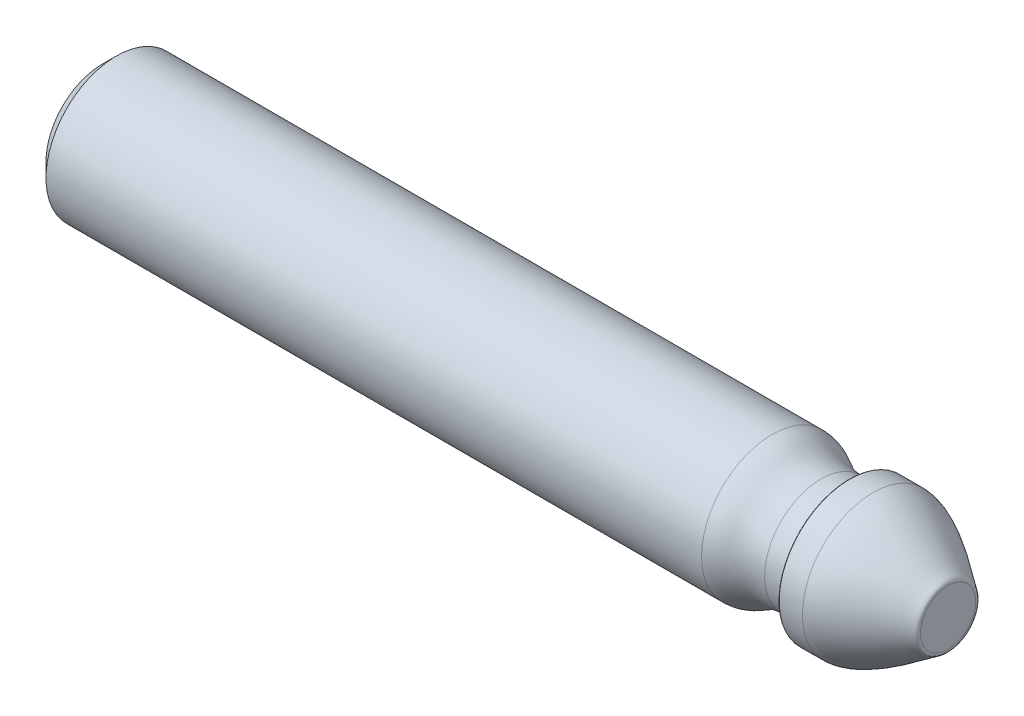
SolidWorks part; units mm, degrees
material "Alloy Steel"
ref_plane "Front" through (0, 0, 0) normal (0, 0, 1) x (1, 0, 0)
ref_plane "Top" through (0, 0, 0) normal (0, 1, 0) x (1, 0, 0)
ref_plane "Right" through (0, 0, 0) normal (1, 0, 0) x (0, 0, -1)
sketch "Sketch1" plane through (0, 0, 0) normal (0, 0, 1) x (1, 0, 0)
  line L0 (-19.05, 0) -> (19.05, 0) construction
  line L1 (19.05, 3.175) -> (19.05, -3.175) construction
  line L2 (-19.05, 3.175) -> (-19.05, -3.175) construction
  dimension "Length" = 38.1
  dimension "Diameter" = 6.35
sketch "Sketch2" plane through (0, 0, 0) normal (1, 0, 0) x (0, 0, -1)
  circle A0 centre (0, 0) radius 3.175
extrude "Extrude1" add sketch "Sketch2" against normal up to vertex (19.05 mm away) and the other way up to vertex (19.05 mm away) up to point (-19.05, 3.175, 0) other way up to point (19.05, 3.175, 0)
chamfer "Chamfer1" distance 0.635 angle 45 2 edges at (19.05, 0, -3.175) (-19.05, 0, -3.175)
sketch "Sketch3" plane through (0, 0, 0) normal (0, 0, 1) x (1, 0, 0)
  line L0 (-19.05, 0) -> (19.05, 0) construction
  line L1 (-19.05, 2.54) -> (-19.05, -2.54) construction
  line L2 (19.05, -2.54) -> (19.05, 2.54) construction
  line L3 (18.415, 3.175) -> (-18.415, 3.175) construction
  line L4 (15.6622, 3.175) -> (14.5934, 3.175)
  line L5 (16.629, 3.175) -> (14.655, 3.175) construction
  line L6 (19.05, 0.802) -> (19.05, 1.6965) construction
  line L7 (19.05, 1.2434) -> (19.05, 3.175)
  line L8 (19.05, 3.175) -> (15.6622, 3.175)
  line L9 (14.5934, 3.175) -> (14.5934, 2.54)
  line L10 (14.5934, 2.54) -> (13.3234, 2.54)
  line L11 (11.1187, 3.175) -> (14.5934, 3.175)
  line L12 (11.6265, 3.175) -> (9.464, 3.175) construction
  line L13 (14.3233, 2.54) -> (12.3233, 2.54) construction
  line L14 (11.1187, 3.175) -> (14.5934, 3.175)
  spline S0 degree 3 poles (15.6622, 3.175) (16.6428, 3.175) (18.614, 1.6311) (19.0441, 1.3825) (19.05, 1.3487) (19.05, 1.2434) knots 0 0 0 0 0.565725 0.665725 1 1 1 1
  spline S1 degree 3 poles (11.1187, 3.175) (11.9879, 3.175) (12.0734, 2.54) (13.3234, 2.54) knots 0 0 0 0 1 1 1 1
  point P24 (11.1187, 3.175)
  point P27 (0, 0)
  point P28 (0, 0)
revolve "Cut-Revolve1" cut sketch "Sketch3" angle 360 about L0 region at (13.3125, 2.889, 0) region at (18.092, 2.592, 0)
fillet "Fillet1" radius 0.0254 1 edges at (14.5934, 0, 3.175)
equation "\"D1@Chamfer1\" = \"Diameter@Sketch1\"*.1"
